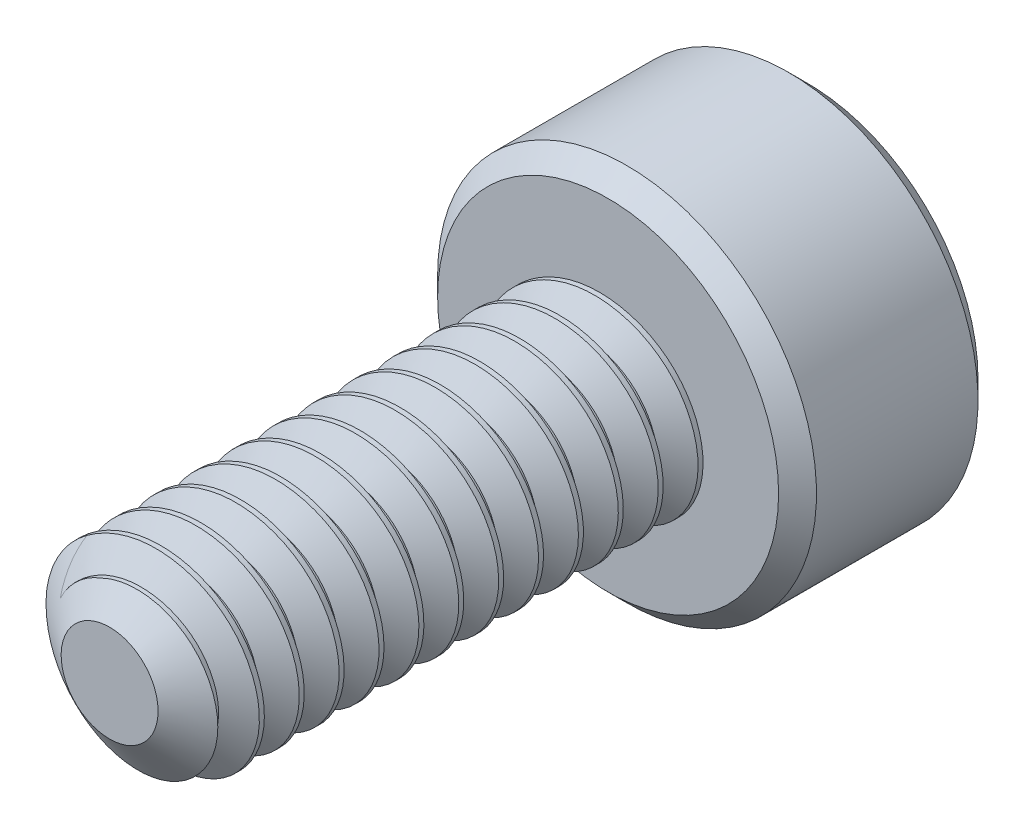
SolidWorks part; units mm, degrees
ref_plane "Front Plane" through (0, 0, 0) normal (0, 0, 1) x (1, 0, 0)
ref_plane "Top Plane" through (0, 0, 0) normal (0, 1, 0) x (1, 0, 0)
ref_plane "Right Plane" through (0, 0, 0) normal (1, 0, 0) x (0, 0, -1)
sketch "Sketch1" plane through (0, 0, 0) normal (0, 0, 1) x (1, 0, 0)
  circle A0 centre (0, 0) radius 1
  dimension "OD" = 2
extrude "Extrude1" add sketch "Sketch1" against normal blind 5
sketch "Sketch2" plane through (0, 0, 0) normal (0, 0, 1) x (1, 0, 0)
  circle A0 centre (0, 0) radius 1 construction
  circle A1 centre (0, 0) radius 1
curve "Helix/Spiral1" pitch 0.4 height 5.4 radius 1 centre (0, 0, 0) axis (0, 0, -1) start towards (0, 1, 0) parameters "pitch"=0.4
sketch "Sketch3" plane through (0, 0, 0) normal (1, 0, 0) x (0, 0, -1)
  line L0 (-0.35, 1) -> (-0.2, 0.7402)
  line L1 (-0.2, 0.7402) -> (-0.15, 0.7402)
  line L2 (-0.15, 0.7402) -> (0, 1)
  line L3 (-0.35, 1) -> (0, 1)
  line L4 (-0.175, 1) -> (-0.175, 0.7402) construction
  line L5 (-0.275, 0.8701) -> (-0.075, 0.8701) construction
  line L6 (0, 1) -> (0, -1) construction
  dimension "D1" = 0.05
  dimension "D2" = 0.2
  dimension "D3" = 60
sweep "Cut-Sweep1" cut profiles "Sketch3" path "Helix/Spiral1"
sketch "Sketch4" plane through (0, 0, 0) normal (1, 0, 0) x (0, 0, -1)
  line L0 (0.3598, 1) -> (0, 0.4862)
  line L1 (0, 0.4862) -> (0, 1)
  line L2 (0.3598, 1) -> (0, 1)
  line L3 (-0.35, 1) -> (0, 1) construction
  line L4 (0, 0) -> (7.0209, 0) construction
  dimension "D1" = 55
  dimension "D2" = 0.254
revolve "Cut-Revolve1" cut sketch "Sketch4" angle 360 about L4
sketch "Sketch5" plane through (0, 0, 0) normal (1, 0, 0) x (0, 0, -1)
  line L0 (5, -0.7135) -> (5, 0.7473) construction
  line L1 (5, 1.127) -> (87.4327, 1.127)
  line L2 (5, 1.127) -> (5, 0)
  line L3 (5, 0) -> (87.3125, 0)
  line L4 (87.3125, 0.7968) -> (87.3125, 0)
  line L5 (87.4327, 1.127) -> (87.3125, 0.7968)
  line L6 (0, 0) -> (9.9695, 0) construction
  point P3 (87.3125, 1.127)
  point P10 (87.3125, 1.127)
  dimension "D1" = 0.3302
  dimension "Thread min" = 87.3125
  dimension "D2" = 0.127
  dimension "D3" = 20
revolve "partially thread" [suppressed] add sketch "Sketch5" angle 360 about L6
sketch "Sketch6" plane through (0, 0, -5) normal (0, 0, -1) x (-1, 0, 0)
  circle A0 centre (0, 0) radius 1.9
  dimension "head dia" = 3.8
extrude "Extrude2" add sketch "Sketch6" along normal blind 2
sketch "Sketch7" plane through (0, 0, -7) normal (0, 0, -1) x (-1, 0, 0)
  line L1 (0, 0.866) -> (-0.75, 0.433)
  line L2 (-0.75, 0.433) -> (-0.75, -0.433)
  line L3 (-0.75, -0.433) -> (0, -0.866)
  line L4 (0, -0.866) -> (0.75, -0.433)
  line L5 (0.75, -0.433) -> (0.75, 0.433)
  line L6 (0.75, 0.433) -> (0, 0.866)
  circle A0 centre (0, 0) radius 0.75 construction
  dimension "hex dia" = 1.5
extrude "Cut-Extrude1" cut sketch "Sketch7" against normal blind 1.125
sketch "Sketch8" plane through (0, 0, -7) normal (0, 0, -1) x (-1, 0, 0)
  circle A0 centre (0, 0) radius 0.866
extrude "Cut-Extrude2" cut sketch "Sketch8" against normal through all draft 45
chamfer "Chamfer1" distance 0.19 angle 45 2 edges at (-1.9, 0, -7) (-1.9, 0, -5)
equation "\"D3@Helix/Spiral1\" = \"screw length@Extrude1\"+\"pitch@Helix/Spiral1\""
equation "\"D1@Sketch3\" = \"pitch@Helix/Spiral1\"*.125"
equation "\"D2@Sketch3\" = \"pitch@Helix/Spiral1\"*.5"
equation "\"D1@Cut-Extrude1\" = \"hex dia@Sketch7\"*.75"
equation "\"D1@Chamfer1\" = \"head dia@Sketch6\"*.05"
